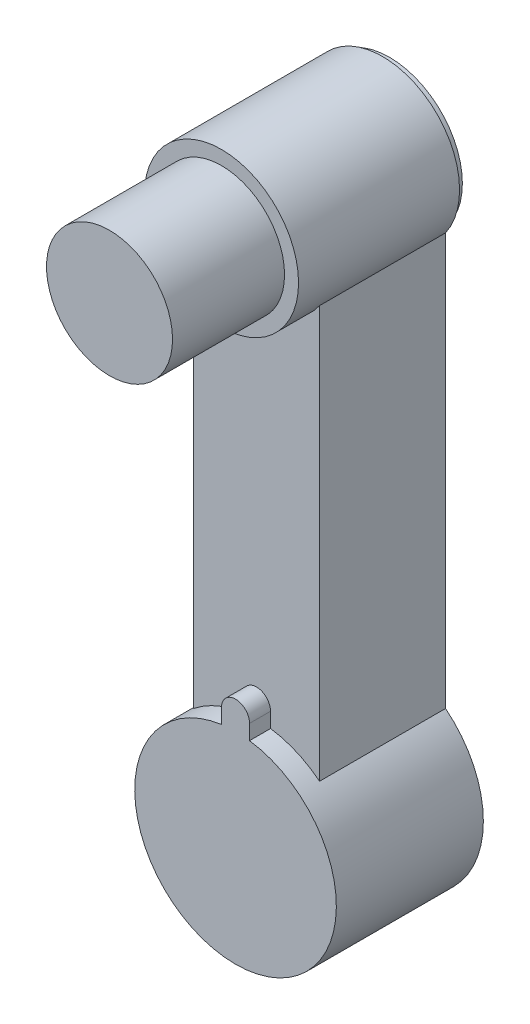
SolidWorks part; units mm, degrees
ref_plane "Front Plane" through (0, 0, 0) normal (0, 0, 1) x (1, 0, 0)
ref_plane "Top Plane" through (0, 0, 0) normal (0, 1, 0) x (1, 0, 0)
ref_plane "Right Plane" through (0, 0, 0) normal (1, 0, 0) x (0, 0, -1)
sketch "Sketch11" plane through (0, 0, 0) normal (0, 0, 1) x (1, 0, 0)
  line L1 (45, 56.205) -> (45, 350.3772)
  line L4 (-45, 56.205) -> (-45, 350.3772)
  circle A0 centre (0, 0) radius 72
  circle A1 centre (0, 382) radius 55
  point P3 (0, 0)
extrude "Boss-Extrude5" add sketch "Sketch11" along normal blind 90 contours A1 L4 A0 L1 region at (0, 200.5283, 0)
extrude "Boss-Extrude6" add sketch "Sketch11<3>" along normal blind 115 contours A1 region at (0, 382, 0)
sketch "Sketch11<3>" plane through (0, 0, 0) normal (0, 0, 1) x (1, 0, 0) same geometry as "Sketch11"
extrude "Boss-Extrude7" add sketch "Sketch11<4>" along normal blind 105 contours A0 region at (0, 0, 0)
sketch "Sketch11<4>" plane through (0, 0, 0) normal (0, 0, 1) x (1, 0, 0) same geometry as "Sketch11"
sketch "Sketch13" plane through (0, 0, 90) normal (0, 0, 1) x (1, 0, 0)
  line L2 (10, 82) -> (10, 71.3022)
  line L3 (10, 71.3022) -> (-10, 71.3022)
  line L4 (-10, 82) -> (-10, 71.3022)
  arc A1 (10, 82) -> (-10, 82) centre (0, 82) ccw
  arc A2 (45, 56.205) -> (-45, 56.205) centre (0, 0) ccw construction
extrude "Boss-Extrude8" add sketch "Sketch13" along normal blind 15
sketch "Sketch17" plane through (0, 0, 115) normal (0, 0, 1) x (1, 0, 0)
  circle A0 centre (0, 382) radius 45
extrude "Boss-Extrude9" add sketch "Sketch17" along normal blind 80
sketch "Sketch18" plane through (0, 0, 0) normal (0, 0, -1) x (-1, 0, 0)
  circle A0 centre (0, 382) radius 52
extrude "Boss-Extrude10" add sketch "Sketch18" along normal blind 5
sketch "Sketch19" plane through (0, 0, -5) normal (0, 0, -1) x (-1, 0, 0)
  circle A0 centre (0, 382) radius 37.5
  circle A1 centre (0, 382) radius 27.5
